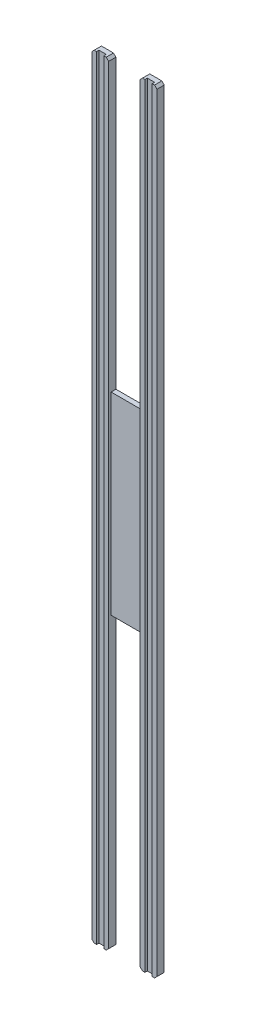
SolidWorks part; units mm, degrees
ref_plane "Piano frontale" through (0, 0, 0) normal (0, 0, 1) x (1, 0, 0)
ref_plane "Piano superiore" through (0, 0, 0) normal (0, 1, 0) x (1, 0, 0)
ref_plane "Piano destro" through (0, 0, 0) normal (1, 0, 0) x (0, 0, -1)
sketch "Schizzo1" plane through (0, 0, 0) normal (0, 0, 1) x (1, 0, 0)
  line L0 (0, 0) -> (0, 80)
  line L1 (0, 80) -> (6.5, 80)
  line L2 (6.5, 80) -> (6.5, 0)
  line L3 (6.5, 0) -> (0, 0)
  dimension "D1" = 6.5
  dimension "D2" = 80
extrude "Estrusione-Estrusione1" add sketch "Schizzo1" along normal blind 2
sketch "Schizzo2" plane through (6.5, 0, 0) normal (1, 0, 0) x (0, 0, -1)
  line L0 (0, 200) -> (-3, 200)
  line L1 (-3, 200) -> (-3, -120)
  line L2 (-3, -120) -> (0, -120)
  line L3 (0, -120) -> (0, 200)
  line L4 (0, 0) -> (0, 80) construction
  line L5 (-2, 80) -> (0, 80) construction
  dimension "D1" = 320
  dimension "D2" = 3
  dimension "D3" = 120
  dimension "D4" = 120
extrude "Estrusione-Estrusione2" add sketch "Schizzo2" along normal blind 7
chamfer "Smusso1" distance 1 angle 45 4 edges at (6.5, -120, 1.5) (13.5, -120, 1.5) (6.5, 200, 1.5) (13.5, 200, 1.5)
sketch "Schizzo4" plane through (0, -120, 0) normal (0, -1, 0) x (1, 0, 0)
  line L0 (8.5, 3) -> (8.5, 2)
  line L1 (12.5, 3) -> (7.5, 3) construction
  line L2 (8.5, 2) -> (11.5, 2)
  line L3 (11.5, 2) -> (11.5, 3)
  line L4 (11.5, 3) -> (8.5, 3)
  line L5 (6.5, 0) -> (6.5, 3) construction
  line L6 (13.5, 3) -> (13.5, 0) construction
  dimension "D1" = 2
  dimension "D2" = 2
  dimension "D3" = 1
extrude "Taglio-Estrusione1" cut sketch "Schizzo4" against normal through all
ref_plane "Piano2" through (0, 0, 0) normal (-1, 0, 0) x (0, 0, 1)
mirror "Specchia9" about plane through (0, 0, 0) normal (-1, 0, 0) of "Taglio-Estrusione1", "Estrusione-Estrusione2", "Estrusione-Estrusione1", "Smusso1"
